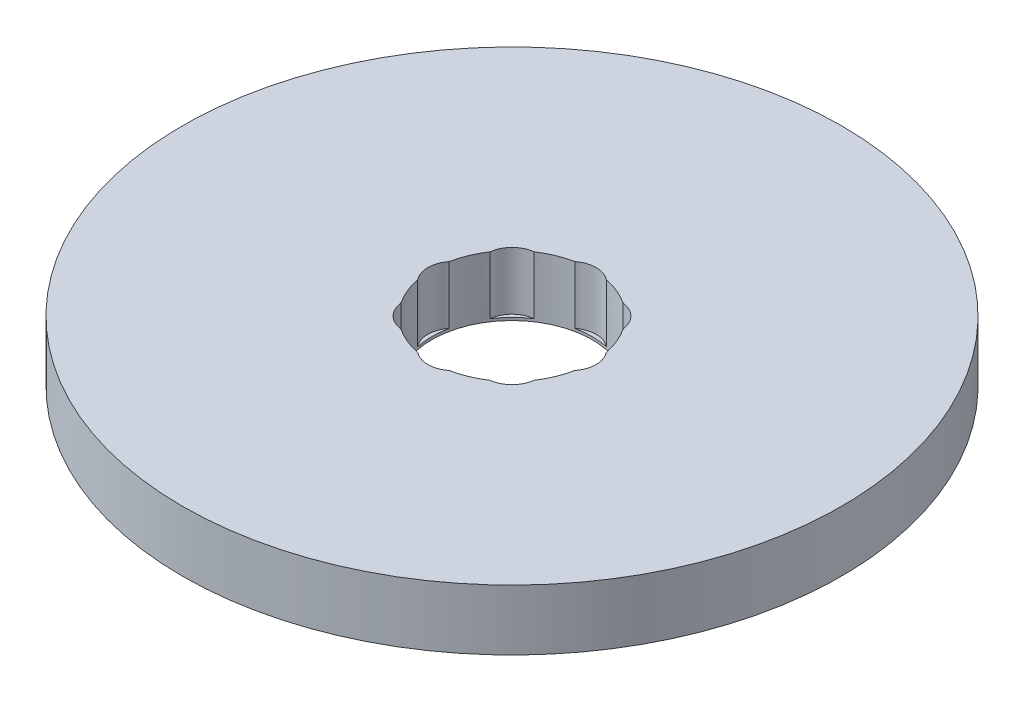
SolidWorks part; units mm, degrees
ref_plane "Front Plane" through (0, 0, 0) normal (0, 0, 1) x (1, 0, 0)
ref_plane "Top Plane" through (0, 0, 0) normal (0, 1, 0) x (1, 0, 0)
ref_plane "Right Plane" through (0, 0, 0) normal (1, 0, 0) x (0, 0, -1)
sketch "Sketch1" plane through (0, 0, 0) normal (0, 1, 0) x (1, 0, 0)
  circle A0 centre (0, 0) radius 92.5
  dimension "FLANGE_OD" = 185
extrude "Boss-Extrude1" add sketch "Sketch1" along normal blind 17
sketch "Sketch2" plane through (0, 0, 0) normal (0, 1, 0) x (1, 0, 0)
  circle A0 centre (0, 0) radius 22.5
  dimension "BORE_D" = 45
extrude "Cut-Extrude1" cut sketch "Sketch2" along normal through all
sketch "Sketch3" plane through (0, 17, 0) normal (0, 1, 0) x (1, 0, 0)
  circle A0 centre (0, 0) radius 16.4925 construction
  circle A1 centre (-16.4925, 0) radius 7.1054
  dimension "BOLT_D" = 14.2107
  dimension "BOLT_PCD" = 32.9849
extrude "Cut-Extrude2" cut sketch "Sketch3" against normal blind 16.2429
pattern_circular "CirPattern1" count 8 over 360 about axis through (0, 0, 0) along (0, 1, 0) of "Cut-Extrude2"
